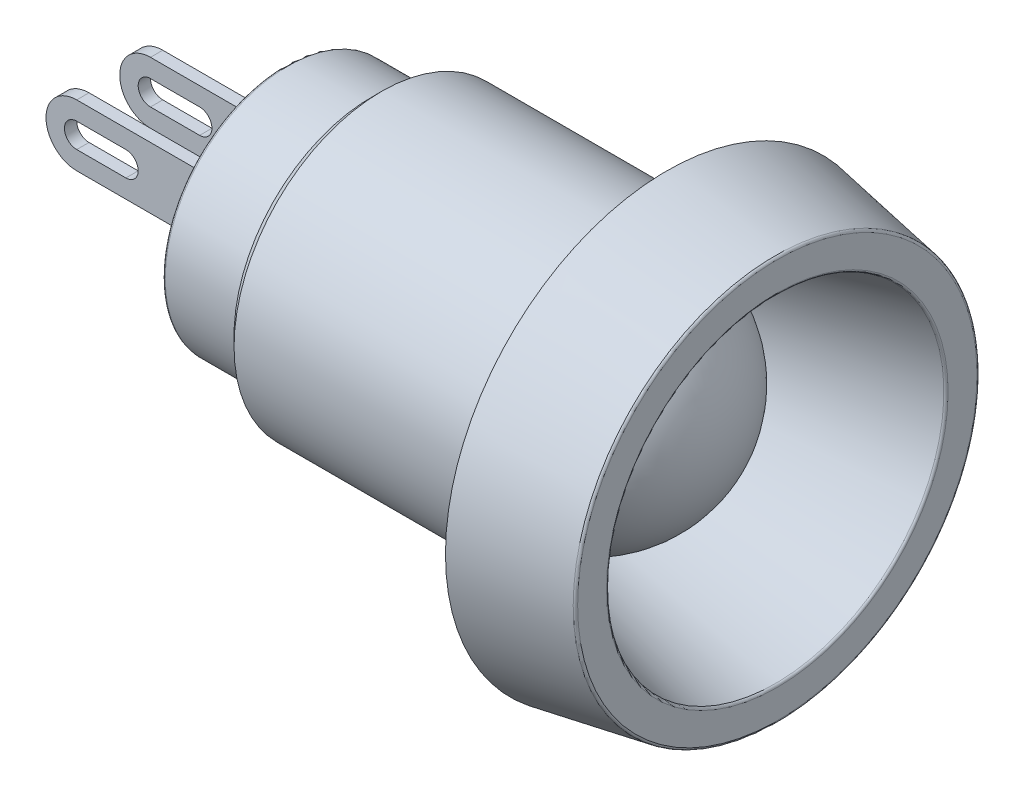
SolidWorks part; units mm, degrees
ref_plane "Спереди" through (0, 0, 0) normal (0, 0, 1) x (1, 0, 0)
ref_plane "Сверху" through (0, 0, 0) normal (0, 1, 0) x (1, 0, 0)
ref_plane "Справа" through (0, 0, 0) normal (1, 0, 0) x (0, 0, -1)
sketch "Эскиз1" plane through (0, 0, 0) normal (0, 0, 1) x (1, 0, 0)
  line L0 (9, 0) -> (30.2381, 0) construction
  line L1 (9, 0) -> (9, 5)
  line L2 (9, 5) -> (12.5, 5)
  line L3 (12.5, 5) -> (12.5, 6)
  line L4 (12.5, 6) -> (24.5, 6)
  line L5 (24.5, 6) -> (24.5, 9)
  line L6 (24.5, 9) -> (29, 8.2065)
  line L7 (29, 8.2065) -> (29, 6.87)
  line L8 (24.5, 9) -> (33.1203, 9) construction
  line L9 (21.5, 5) -> (29, 6.87)
  line L10 (9, 0) -> (26.5, 0)
  arc A0 (21.5, 5) -> (26.5, 0) centre (21.5, 0) cw
  dimension "D7" = 5
  dimension "D1" = 4.5
  dimension "D2" = 20
  dimension "D3" = 12
  dimension "D4" = 12
  dimension "D5" = 10
  dimension "D6" = 18
  dimension "D8" = 2.5
  dimension "D9" = 10
  dimension "D10" = 14
revolve "Повернуть1" add sketch "Эскиз1" angle 360 about L10
chamfer "Фаска1" distance 0.4 angle 45 1 edges at (12.5, 0, 6)
sketch "Эскиз2" plane through (12.5, 0, 0) normal (-1, 0, 0) x (0, 0, 1)
  circle A0 centre (0, 0) radius 3.73
  dimension "D1" = 7.46
curve "Спираль1" pitch 0.5 height 11.75 turns 23.5
sketch "Эскиз3" plane through (0, 0, 0) normal (0, 1, 0) x (1, 0, 0)
  line L0 (12.5043, -3.7246) -> (12.5043, -4.6572) construction
  line L1 (12.5043, -3.7246) -> (12.7043, -4.071)
  line L2 (12.7043, -4.071) -> (12.3043, -4.071)
  line L3 (12.5043, -3.7246) -> (12.3043, -4.071)
  spline S0 degree 3 poles (12.5, -3.73) (12.5103, -3.73) (12.5313, -3.5358) (12.5625, -2.7062) (12.5938, -1.4646) (12.625, 0) (12.6563, 1.4646) (12.6875, 2.7062) (12.7188, 3.5358) (12.75, 3.8271) (12.7813, 3.5358) (12.8125, 2.7062) (12.8438, 1.4646) (12.875, 0) (12.9063, -1.4646) (12.9375, -2.7062) (12.9688, -3.5358) (13, -3.8271) (13.0313, -3.5358) (13.0625, -2.7062) (13.0938, -1.4646) (13.125, 0) (13.1563, 1.4646) (13.1875, 2.7062) (13.2188, 3.5358) (13.25, 3.8271) (13.2813, 3.5358) (13.3125, 2.7062) (13.3438, 1.4646) (13.375, 0) (13.4063, -1.4646) (13.4375, -2.7062) (13.4688, -3.5358) (13.5, -3.8271) (13.5313, -3.5358) (13.5625, -2.7062) (13.5938, -1.4646) (13.625, 0) (13.6563, 1.4646) (13.6875, 2.7062) (13.7188, 3.5358) (13.75, 3.8271) (13.7813, 3.5358) (13.8125, 2.7062) (13.8438, 1.4646) (13.875, 0) (13.9063, -1.4646) (13.9375, -2.7062) (13.9688, -3.5358) (14, -3.8271) (14.0312, -3.5358) (14.0625, -2.7062) (14.0938, -1.4646) (14.125, 0) (14.1563, 1.4646) (14.1875, 2.7062) (14.2188, 3.5358) (14.25, 3.8271) (14.2813, 3.5358) (14.3125, 2.7062) (14.3438, 1.4646) (14.375, 0) (14.4062, -1.4646) (14.4375, -2.7062) (14.4688, -3.5358) (14.5, -3.8271) (14.5313, -3.5358) (14.5625, -2.7062) (14.5938, -1.4646) (14.625, 0) (14.6563, 1.4646) (14.6875, 2.7062) (14.7188, 3.5358) (14.75, 3.8271) (14.7813, 3.5358) (14.8125, 2.7062) (14.8438, 1.4646) (14.875, 0) (14.9063, -1.4646) (14.9375, -2.7062) (14.9688, -3.5358) (15, -3.8271) (15.0313, -3.5358) (15.0625, -2.7062) (15.0938, -1.4646) (15.125, 0) (15.1563, 1.4646) (15.1875, 2.7062) (15.2188, 3.5358) (15.25, 3.8271) (15.2813, 3.5358) (15.3125, 2.7062) (15.3438, 1.4646) (15.375, 0) (15.4063, -1.4646) (15.4375, -2.7062) (15.4688, -3.5358) (15.5, -3.8271) (15.5313, -3.5358) (15.5625, -2.7062) (15.5938, -1.4646) (15.625, 0) (15.6563, 1.4646) (15.6875, 2.7062) (15.7188, 3.5358) (15.75, 3.8271) (15.7813, 3.5358) (15.8125, 2.7062) (15.8438, 1.4646) (15.875, 0) (15.9062, -1.4646) (15.9375, -2.7062) (15.9688, -3.5358) (16, -3.8271) (16.0313, -3.5358) (16.0625, -2.7062) (16.0938, -1.4646) (16.125, 0) (16.1563, 1.4646) (16.1875, 2.7062) (16.2188, 3.5358) (16.25, 3.8271) (16.2813, 3.5358) (16.3125, 2.7062) (16.3438, 1.4646) (16.375, 0) (16.4063, -1.4646) (16.4375, -2.7062) (16.4688, -3.5358) (16.5, -3.8271) (16.5312, -3.5358) (16.5625, -2.7062) (16.5938, -1.4646) (16.625, 0) (16.6563, 1.4646) (16.6875, 2.7062) (16.7188, 3.5358) (16.75, 3.8271) (16.7813, 3.5358) (16.8125, 2.7062) (16.8438, 1.4646) (16.875, 0) (16.9062, -1.4646) (16.9375, -2.7062) (16.9688, -3.5358) (17, -3.8271) (17.0312, -3.5358) (17.0625, -2.7062) (17.0938, -1.4646) (17.125, 0) (17.1562, 1.4646) (17.1875, 2.7062) (17.2188, 3.5358) (17.25, 3.8271) (17.2812, 3.5358) (17.3125, 2.7062) (17.3438, 1.4646) (17.375, 0) (17.4063, -1.4646) (17.4375, -2.7062) (17.4688, -3.5358) (17.5, -3.8271) (17.5313, -3.5358) (17.5625, -2.7062) (17.5938, -1.4646) (17.625, 0) (17.6563, 1.4646) (17.6875, 2.7062) (17.7188, 3.5358) (17.75, 3.8271) (17.7813, 3.5358) (17.8125, 2.7062) (17.8438, 1.4646) (17.875, 0) (17.9063, -1.4646) (17.9375, -2.7062) (17.9688, -3.5358) (18, -3.8271) (18.0313, -3.5358) (18.0625, -2.7062) (18.0938, -1.4646) (18.125, 0) (18.1563, 1.4646) (18.1875, 2.7062) (18.2188, 3.5358) (18.25, 3.8271) (18.2813, 3.5358) (18.3125, 2.7062) (18.3438, 1.4646) (18.375, 0) (18.4063, -1.4646) (18.4375, -2.7062) (18.4688, -3.5358) (18.5, -3.8271) (18.5313, -3.5358) (18.5625, -2.7062) (18.5938, -1.4646) (18.625, 0) (18.6563, 1.4646) (18.6875, 2.7062) (18.7188, 3.5358) (18.75, 3.8271) (18.7813, 3.5358) (18.8125, 2.7062) (18.8438, 1.4646) (18.875, 0) (18.9063, -1.4646) (18.9375, -2.7062) (18.9688, -3.5358) (19, -3.8271) (19.0313, -3.5358) (19.0625, -2.7062) (19.0938, -1.4646) (19.125, 0) (19.1563, 1.4646) (19.1875, 2.7062) (19.2188, 3.5358) (19.25, 3.8271) (19.2813, 3.5358) (19.3125, 2.7062) (19.3438, 1.4646) (19.375, 0) (19.4063, -1.4646) (19.4375, -2.7062) (19.4688, -3.5358) (19.5, -3.8271) (19.5313, -3.5358) (19.5625, -2.7062) (19.5938, -1.4646) (19.625, 0) (19.6563, 1.4646) (19.6875, 2.7062) (19.7188, 3.5358) (19.75, 3.8271) (19.7813, 3.5358) (19.8125, 2.7062) (19.8438, 1.4646) (19.875, 0) (19.9062, -1.4646) (19.9375, -2.7062) (19.9688, -3.5358) (20, -3.8271) (20.0313, -3.5358) (20.0625, -2.7062) (20.0938, -1.4646) (20.125, 0) (20.1563, 1.4646) (20.1875, 2.7062) (20.2188, 3.5358) (20.25, 3.8271) (20.2813, 3.5358) (20.3125, 2.7062) (20.3438, 1.4646) (20.375, 0) (20.4063, -1.4646) (20.4375, -2.7062) (20.4688, -3.5358) (20.5, -3.8271) (20.5313, -3.5358) (20.5625, -2.7062) (20.5938, -1.4646) (20.625, 0) (20.6563, 1.4646) (20.6875, 2.7062) (20.7188, 3.5358) (20.75, 3.8271) (20.7813, 3.5358) (20.8125, 2.7062) (20.8438, 1.4646) (20.875, 0) (20.9063, -1.4646) (20.9375, -2.7062) (20.9688, -3.5358) (21, -3.8271) (21.0313, -3.5358) (21.0625, -2.7062) (21.0938, -1.4646) (21.125, 0) (21.1563, 1.4646) (21.1875, 2.7062) (21.2188, 3.5358) (21.25, 3.8271) (21.2813, 3.5358) (21.3125, 2.7062) (21.3438, 1.4646) (21.375, 0) (21.4063, -1.4646) (21.4375, -2.7062) (21.4688, -3.5358) (21.5, -3.8271) (21.5313, -3.5358) (21.5625, -2.7062) (21.5938, -1.4646) (21.625, 0) (21.6563, 1.4646) (21.6875, 2.7062) (21.7188, 3.5358) (21.75, 3.8271) (21.7813, 3.5358) (21.8125, 2.7062) (21.8438, 1.4646) (21.875, 0) (21.9063, -1.4646) (21.9375, -2.7062) (21.9688, -3.5358) (22, -3.8271) (22.0313, -3.5358) (22.0625, -2.7062) (22.0938, -1.4646) (22.125, 0) (22.1563, 1.4646) (22.1875, 2.7062) (22.2188, 3.5358) (22.25, 3.8271) (22.2813, 3.5358) (22.3125, 2.7062) (22.3438, 1.4646) (22.375, 0) (22.4063, -1.4646) (22.4375, -2.7062) (22.4688, -3.5358) (22.5, -3.8271) (22.5313, -3.5358) (22.5625, -2.7062) (22.5938, -1.4646) (22.625, 0) (22.6563, 1.4646) (22.6875, 2.7062) (22.7188, 3.5358) (22.75, 3.8271) (22.7813, 3.5358) (22.8125, 2.7062) (22.8438, 1.4646) (22.875, 0) (22.9063, -1.4646) (22.9375, -2.7062) (22.9688, -3.5358) (23, -3.8271) (23.0313, -3.5358) (23.0625, -2.7062) (23.0938, -1.4646) (23.125, 0) (23.1563, 1.4646) (23.1875, 2.7062) (23.2188, 3.5358) (23.25, 3.8271) (23.2813, 3.5358) (23.3125, 2.7062) (23.3438, 1.4646) (23.375, 0) (23.4063, -1.4646) (23.4375, -2.7062) (23.4688, -3.5358) (23.5, -3.8271) (23.5313, -3.5358) (23.5625, -2.7062) (23.5938, -1.4646) (23.625, 0) (23.6563, 1.4646) (23.6875, 2.7062) (23.7187, 3.5358) (23.75, 3.8271) (23.7812, 3.5358) (23.8125, 2.7062) (23.8437, 1.4646) (23.875, 0) (23.9062, -1.4646) (23.9375, -2.7062) (23.9687, -3.5358) (24, -3.8271) (24.0312, -3.5358) (24.0625, -2.7062) (24.0937, -1.4646) (24.125, 0) (24.1562, 1.4646) (24.1875, 2.7062) (24.2187, 3.5358) (24.2397, 3.73) (24.25, 3.73) knots 0 0 0 0 0.00266 0.005319 0.007979 0.010638 0.013298 0.015957 0.018617 0.021277 0.023936 0.026596 0.029255 0.031915 0.034574 0.037234 0.039894 0.042553 0.045213 0.047872 0.050532 0.053191 0.055851 0.058511 0.06117 0.06383 0.066489 0.069149 0.071809 0.074468 0.077128 0.079787 0.082447 0.085106 0.087766 0.090426 0.093085 0.095745 0.098404 0.101064 0.103723 0.106383 0.109043 0.111702 0.114362 0.117021 0.119681 0.12234 0.125 0.12766 0.130319 0.132979 0.135638 0.138298 0.140957 0.143617 0.146277 0.148936 0.151596 0.154255 0.156915 0.159574 0.162234 0.164894 0.167553 0.170213 0.172872 0.175532 0.178191 0.180851 0.183511 0.18617 0.18883 0.191489 0.194149 0.196809 0.199468 0.202128 0.204787 0.207447 0.210106 0.212766 0.215426 0.218085 0.220745 0.223404 0.226064 0.228723 0.231383 0.234043 0.236702 0.239362 0.242021 0.244681 0.24734 0.25 0.25266 0.255319 0.257979 0.260638 0.263298 0.265957 0.268617 0.271277 0.273936 0.276596 0.279255 0.281915 0.284574 0.287234 0.289894 0.292553 0.295213 0.297872 0.300532 0.303191 0.305851 0.308511 0.31117 0.31383 0.316489 0.319149 0.321809 0.324468 0.327128 0.329787 0.332447 0.335106 0.337766 0.340426 0.343085 0.345745 0.348404 0.351064 0.353723 0.356383 0.359043 0.361702 0.364362 0.367021 0.369681 0.37234 0.375 0.37766 0.380319 0.382979 0.385638 0.388298 0.390957 0.393617 0.396277 0.398936 0.401596 0.404255 0.406915 0.409574 0.412234 0.414894 0.417553 0.420213 0.422872 0.425532 0.428191 0.430851 0.433511 0.43617 0.43883 0.441489 0.444149 0.446809 0.449468 0.452128 0.454787 0.457447 0.460106 0.462766 0.465426 0.468085 0.470745 0.473404 0.476064 0.478723 0.481383 0.484043 0.486702 0.489362 0.492021 0.494681 0.49734 0.5 0.50266 0.505319 0.507979 0.510638 0.513298 0.515957 0.518617 0.521277 0.523936 0.526596 0.529255 0.531915 0.534574 0.537234 0.539894 0.542553 0.545213 0.547872 0.550532 0.553191 0.555851 0.558511 0.56117 0.56383 0.566489 0.569149 0.571809 0.574468 0.577128 0.579787 0.582447 0.585106 0.587766 0.590426 0.593085 0.595745 0.598404 0.601064 0.603723 0.606383 0.609043 0.611702 0.614362 0.617021 0.619681 0.62234 0.625 0.62766 0.630319 0.632979 0.635638 0.638298 0.640957 0.643617 0.646277 0.648936 0.651596 0.654255 0.656915 0.659574 0.662234 0.664894 0.667553 0.670213 0.672872 0.675532 0.678191 0.680851 0.683511 0.68617 0.68883 0.691489 0.694149 0.696809 0.699468 0.702128 0.704787 0.707447 0.710106 0.712766 0.715426 0.718085 0.720745 0.723404 0.726064 0.728723 0.731383 0.734043 0.736702 0.739362 0.742021 0.744681 0.74734 0.75 0.75266 0.755319 0.757979 0.760638 0.763298 0.765957 0.768617 0.771277 0.773936 0.776596 0.779255 0.781915 0.784574 0.787234 0.789894 0.792553 0.795213 0.797872 0.800532 0.803191 0.805851 0.808511 0.81117 0.81383 0.816489 0.819149 0.821809 0.824468 0.827128 0.829787 0.832447 0.835106 0.837766 0.840426 0.843085 0.845745 0.848404 0.851064 0.853723 0.856383 0.859043 0.861702 0.864362 0.867021 0.869681 0.87234 0.875 0.87766 0.880319 0.882979 0.885638 0.888298 0.890957 0.893617 0.896277 0.898936 0.901596 0.904255 0.906915 0.909574 0.912234 0.914894 0.917553 0.920213 0.922872 0.925532 0.928191 0.930851 0.933511 0.93617 0.93883 0.941489 0.944149 0.946809 0.949468 0.952128 0.954787 0.957447 0.960106 0.962766 0.965426 0.968085 0.970745 0.973404 0.976064 0.978723 0.981383 0.984043 0.986702 0.989362 0.992021 0.994681 0.99734 1 1 1 1 construction
  point P7 (12.5043, -4.071)
  dimension "D1" = 60
  dimension "D2" = 0.4
sweep "Вырез-По траектории1" [suppressed] cut profiles "Эскиз3" path "Спираль1"
fillet "Скругление1" radius 0.1 3 edges at (9, 0, 5) (29, 0, 6.87) (29, 0, 8.2065)
sketch "Эскиз4" plane through (9, 0, 0) normal (-1, 0, 0) x (0, 0, 1)
  line L0 (0, 0) -> (0, -4.9) construction
  line L1 (0, 0) -> (-9, 0) construction
  line L2 (1.25, 1.25) -> (1.75, 1.25)
  line L3 (-1.25, -1.25) -> (-1.75, -1.25)
  line L4 (-1.25, -1.25) -> (-1.25, 1.25)
  line L5 (-1.25, 1.25) -> (-1.75, 1.25)
  line L6 (-1.75, -1.25) -> (-1.75, 1.25)
  line L7 (-1.25, -1.25) -> (-1.75, 1.25) construction
  line L8 (-1.25, 1.25) -> (-1.75, -1.25) construction
  line L9 (1.75, -1.25) -> (1.75, 1.25)
  line L10 (1.25, -1.25) -> (1.75, -1.25)
  line L11 (1.25, -1.25) -> (1.25, 1.25)
  line L12 (1.25, 1.25) -> (1.75, -1.25) construction
  line L13 (1.25, -1.25) -> (1.75, 1.25) construction
  circle A0 centre (0, 0) radius 4.9 construction
  circle A1 centre (0, 0) radius 9 construction
  point P5 (-1.5, 0)
  point P18 (1.5, 0)
  dimension "D1" = 3
  dimension "D2" = 0.5
  dimension "D3" = 2.5
extrude "Бобышка-Вытянуть1" add sketch "Эскиз4" along normal blind 8 contours L11 L10 L9 L2 | L4 L5 L6 L3 region at (9, 0, 1.5)
fillet "Скругление2" radius 1.25 4 edges at (1, -1.25, 1.5) (1, -1.25, -1.5) (1, 1.25, 1.5) (1, 1.25, -1.5)
sketch "Эскиз5" plane through (0, 0, -1.75) normal (0, 0, -1) x (-1, 0, 0)
  line L0 (-4.25, 0.5) -> (-2.25, 0.5)
  line L1 (-4.25, -0.5) -> (-2.25, -0.5)
  arc A0 (-2.25, -0.5) -> (-2.25, 0.5) centre (-2.25, 0) ccw
  arc A1 (-4.25, 0.5) -> (-4.25, -0.5) centre (-4.25, 0) ccw
  dimension "D1" = 1
  dimension "D2" = 2
extrude "Вырез-Вытянуть1" cut sketch "Эскиз5" against normal through all
